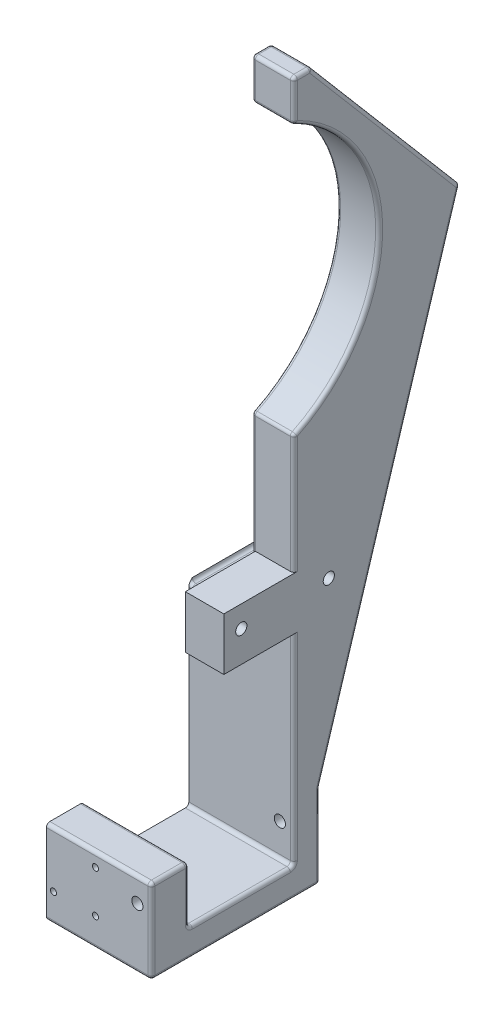
SolidWorks part; units mm, degrees
note: The reader was unsure of these and kept them because the rebuilt part matched: shared geometry of "Sketch12<3>".
ref_plane "Front Plane" through (0, 0, 0) normal (0, 0, 1) x (1, 0, 0)
ref_plane "Top Plane" through (0, 0, 0) normal (0, 1, 0) x (1, 0, 0)
ref_plane "Right Plane" through (0, 0, 0) normal (1, 0, 0) x (0, 0, -1)
sketch "Sketch3" plane through (0, 0, 0) normal (0, 1, 0) x (1, 0, 0)
  line L1 (-55.92, 48.2) -> (0, 48.2)
  line L2 (-55.92, 48.2) -> (-55.92, 0)
  line L3 (-55.92, 0) -> (0, 0)
  line L4 (0, 48.2) -> (0, 0)
  dimension "D1" = 55.92
  dimension "D2" = 48.2
extrude "Boss-Extrude1" add sketch "Sketch3" along normal blind 8
sketch "Sketch4" plane through (0, 8, 0) normal (0, 1, 0) x (1, 0, 0)
  line L0 (-55.92, 0) -> (-55.92, 48.2)
  line L9 (-55.92, 48.2) -> (0, 48.2)
  line L10 (0, 48.2) -> (0, 40.7)
  line L11 (0, 40.7) -> (-48.42, 40.7)
  line L12 (-48.42, 40.7) -> (-48.42, 0)
  line L13 (-48.42, 0) -> (-55.92, 0)
  line L14 (0, 48.2) -> (-55.92, 48.2) construction
  line L15 (-55.92, 48.2) -> (-55.92, 0) construction
  line L16 (-55.92, 0) -> (0, 0) construction
  line L17 (0, 0) -> (0, 48.2) construction
  dimension "D1" = 7.5
extrude "Boss-Extrude2" add sketch "Sketch4" along normal blind 95
sketch "Sketch5" plane through (-48.42, 0, 0) normal (1, 0, 0) x (0, 0, -1)
  line L0 (0, 103) -> (0, 8) construction
  line L1 (0, 82.4) -> (40.7, 82.4)
  line L2 (0, 82.4) -> (0, 17.6)
  line L3 (0, 17.6) -> (40.7, 17.6)
  line L4 (40.7, 82.4) -> (40.7, 17.6)
  line L5 (40.7, 103) -> (40.7, 8) construction
  line L7 (0, 8) -> (40.7, 8) construction
  line L8 (0, 50) -> (40.7, 50) construction
  circle A0 centre (17.2, 12.5) radius 2.75
  circle A1 centre (34.2, 12.5) radius 2.75
  circle A2 centre (34.2, 87.5) radius 2.75
  circle A3 centre (17.2, 87.5) radius 2.75
  dimension "D3" = 5.5
  dimension "D1" = 4.5
  dimension "D2" = 64.8
  dimension "D4" = 17
  dimension "D5" = 5.1
  dimension "D6" = 6.5
  dimension "D7" = 75
extrude "Cut-Extrude1" cut sketch "Sketch5" against normal through all
sketch "Sketch8" plane through (0, 0, 0) normal (1, 0, 0) x (0, 0, -1)
  line L0 (40.7, 103) -> (40.7, 203)
  line L1 (40.7, 203) -> (45.7, 203)
  line L2 (45.7, 203) -> (88.2, 153)
  line L3 (88.2, 153) -> (48.2, 24)
  line L4 (48.2, 24) -> (48.2, 103)
  line L5 (48.2, 103) -> (40.7, 103)
  line L6 (40.7, 103) -> (48.2, 103) construction
  line L7 (48.2, 103) -> (48.2, 0) construction
  line L8 (40.7, 103) -> (40.7, 8) construction
  point P25 (40.7, 153)
  dimension "D1" = 100
  dimension "D2" = 5
  dimension "D3" = 40
  dimension "D4" = 24
extrude "Boss-Extrude4" add sketch "Sketch8" against normal blind 55.92
sketch "Sketch9" plane through (0, 0, 0) normal (1, 0, 0) x (0, 0, -1)
  line L0 (88.2, 153) -> (45.7, 203) construction
  circle A0 centre (22.578, 153) radius 42.5
  dimension "D1" = 85
  dimension "D2" = 50
extrude "Cut-Extrude2" cut sketch "Sketch9" against normal through all
sketch "Sketch10" plane through (0, 0, -40.7) normal (0, 0, 1) x (1, 0, 0)
  line L0 (-55.92, 103) -> (-48.42, 103) construction
  line L1 (-30, 203) -> (-12, 203)
  line L2 (-30, 203) -> (-30, 63)
  line L3 (-30, 63) -> (-12, 63)
  line L4 (-12, 203) -> (-12, 63)
  line L5 (0, 114.5573) -> (0, 191.4427) construction
  line L8 (-55.92, 203) -> (0, 203) construction
  line L10 (-55.92, 203) -> (-42, 203)
  line L11 (-42, 203) -> (-42, 103)
  line L12 (-42, 103) -> (-55.92, 103)
  line L13 (-55.92, 103) -> (-55.92, 203)
  line L14 (-55.92, 191.4427) -> (-55.92, 114.5573) construction
  point P11 (-21, 203)
  dimension "D1" = 18
  dimension "D2" = 42
  dimension "D3" = 21
  dimension "D4" = 140
extrude "Cut-Extrude3" cut sketch "Sketch10" against normal through all
sketch "Sketch11" plane through (0, 8, 0) normal (0, 1, 0) x (1, 0, 0)
  line L0 (0, 0) -> (0, 40.7) construction
  line L1 (0, 0) -> (-48.42, 0)
  line L2 (0, 0) -> (0, 10.7)
  line L3 (0, 10.7) -> (-48.42, 10.7)
  line L4 (-48.42, 0) -> (-48.42, 10.7)
  line L5 (-55.92, 0) -> (-48.42, 0) construction
  line L6 (-48.42, 0) -> (-48.42, 40.7) construction
  dimension "D1" = 10.7
extrude "Boss-Extrude5" add sketch "Sketch11" along normal blind 16
sketch "Sketch12" plane through (0, 0, 0) normal (0, 0, 1) x (1, 0, 0)
  line L0 (-27.96, 20.15) -> (-27.96, -0.9173) construction
  line L1 (-39.96, 20.15) -> (-15.96, 20.15) construction
  line L2 (-48.42, 24) -> (0, 24) construction
  line L3 (-55.92, 0) -> (0, 0) construction
  circle A0 centre (-39.96, 8.15) radius 0.875
  circle A1 centre (-39.96, 20.15) radius 0.875
  circle A2 centre (-27.96, 8.15) radius 0.875
  circle A3 centre (-15.96, 8.15) radius 0.875
  circle A4 centre (-15.96, 20.15) radius 0.875
  point P21 (-27.96, 0)
  dimension "D1" = 1.75
  dimension "D2" = 24
  dimension "D3" = 12
  dimension "D4" = 3.85
extrude "Cut-Extrude7" cut sketch "Sketch12" against normal blind 8
extrude "Cut-Extrude8" cut sketch "Sketch12<3>" along normal blind 5 from surface at -48.2 starting at face at (-27.96, 12, -48.2)
sketch "Sketch12<3>" plane through (0, 0, 0) normal (0, 0, 1) x (1, 0, 0) same geometry as "Sketch12"
fillet "Fillet3" radius 1 80 edges at (-36, 191.4427, -40.7) (-6, 191.4427, -40.7) (-42, 153, -65.078) (-12, 153, -65.078) (-30, 153, -65.078) (-36, 153, -88.2) (-6, 153, -88.2) (-48.96, 103, -72.6961) (-21, 63, -60.293) (-36, 203, -45.7) (-6, 203, -45.7) (-36, 203, -40.7) (-6, 203, -40.7) (-30, 178, -66.95) (-30, 108, -74.2465) (-30, 63, -50.4965) (-12, 178, -66.95) (-12, 108, -74.2465) (-12, 203, -43.2) (-12, 88.7786, -40.7) (-30, 88.7786, -40.7) (-21, 63, -40.7) (-30, 197.2214, -40.7) (-12, 197.2214, -40.7) (-30, 203, -43.2) (-12, 63, -50.4965) (-42, 178, -66.95) (-42, 128, -80.4481) (-42, 203, -43.2) (-42, 197.2214, -40.7) (-45.21, 103, -40.7) (-42, 108.7786, -40.7) (-42, 103, -56.6981) (-48.42, 17.6, -25.7) (-48.42, 8, -25.7) (0, 8, -25.7) (-48.42, 20.8, -10.7) (-24.21, 8, -10.7) (-48.42, 92.7, 0) (0, 16, -10.7) (-48.42, 12.8, -10.7) (-48.42, 20.8, 0) (-24.21, 8, -40.7) (0, 24, -5.35) (-24.21, 24, -10.7) (-48.42, 24, -5.35) (-24.21, 24, 0) (-48.42, 92.7, -40.7) (0, 197.2214, -40.7) (-52.17, 103, 0) (-48.42, 103, -20.35) (-48.42, 12.8, -40.7) (-55.92, 8.8, 0) (-27.96, 0, -48.2) (-52.17, 17.6, 0) (-55.92, 82.4, -20.35) (-52.17, 82.4, 0) (-55.92, 50, -40.7) (-52.17, 82.4, -40.7) (-55.92, 17.6, -20.35) (-52.17, 17.6, -40.7) (-48.42, 17.6, -5.35) (0, 0, -24.1) (-48.42, 82.4, -20.35) (-27.96, 0, 0) (-55.92, 0, -24.1) (-55.92, 103, -36.3481) (-55.92, 12, -48.2) (0, 12, -48.2) (-55.92, 63.5, -60.4481) (-27.96, 24, -48.2) (0, 88.5, -68.2) (0, 178, -66.95) (0, 203, -43.2) (0, 12, 0) (-55.92, 92.7, 0) (0, 61.2786, -40.7) (-6, 114.5573, -40.7) (0, 153, -65.078) (-36, 114.5573, -40.7)
sketch "Sketch14" plane through (0, 0, -48.2) normal (0, 0, -1) x (-1, 0, 0)
  line L0 (1, 23.8485) -> (1, 1) construction
  line L1 (54.92, 23.8485) -> (1, 23.8485) construction
  circle A0 centre (4, 17.2285) radius 1.6
  dimension "D1" = 3.2
  dimension "D2" = 3
  dimension "D3" = 6.62
extrude "Cut-Extrude9" cut sketch "Sketch14" against normal up to surface (48.2 mm away)
sketch "Sketch15" plane through (0, 0, -40.7) normal (0, 0, 1) x (1, 0, 0)
  line L0 (-11, 113.9283) -> (-11, 64) construction
  line L1 (-11, 80.5) -> (0, 80.5)
  line L2 (-11, 80.5) -> (-11, 65.5)
  line L3 (-11, 65.5) -> (0, 65.5)
  line L4 (0, 80.5) -> (0, 65.5)
  line L6 (-1, 8) -> (-47.42, 8) construction
  line L7 (0, 113.9283) -> (0, 9) construction
  dimension "D1" = 57.5
  dimension "D2" = 72.5
extrude "Boss-Extrude6" add sketch "Sketch15" along normal blind 20 and the other way up to next
sketch "Sketch16" plane through (0, 0, 0) normal (1, 0, 0) x (0, 0, -1)
  line L0 (20.7, 65.5) -> (20.7, 80.5) construction
  line L2 (1, 24) -> (9.7, 24) construction
  circle A0 centre (25.69, 74.3259) radius 1.6
  circle A1 centre (50.69, 74.3259) radius 1.6
  dimension "D1" = 3.2
  dimension "D4" = 25
  dimension "D2" = 4.99
  dimension "D3" = 50.3259
extrude "Cut-Extrude10" cut sketch "Sketch16" against normal up to next
sketch "Sketch17" plane through (0, 0, -40.7) normal (0, 0, 1) x (1, 0, 0)
  line L0 (-30, 113.9283) -> (-30, 64) construction
  line L1 (-30, 529.4052) -> (-288.1725, 529.4052)
  line L2 (-30, 529.4052) -> (-30, -248.908)
  line L3 (-30, -248.908) -> (-288.1725, -248.908)
  line L4 (-288.1725, 529.4052) -> (-288.1725, -248.908)
  point P4 (45.9584, 224.1908)
ref_plane "Plane1" through (-30, 0, 0) normal (1, 0, 0) x (0, 0, -1)
sketch "Sketch21" plane through (-30, 0, 0) normal (1, 0, 0) x (0, 0, -1)
  line L0 (45.7, 50) -> (48.2, 54.3301)
  line L1 (48.2, 54.3301) -> (50.7, 50)
  line L2 (50.7, 50) -> (45.7, 50)
  line L3 (43.2, 35) -> (48.2, 35)
  line L4 (48.2, 35) -> (45.7, 30.6699)
  line L5 (45.7, 30.6699) -> (43.2, 35)
  line L6 (45.7, 2.5) -> (40.7, 2.5)
  line L7 (40.7, 2.5) -> (43.2, 6.8301)
  line L8 (43.2, 6.8301) -> (45.7, 2.5)
  line L9 (2.85, 20.5) -> (7.85, 20.5)
  line L10 (7.85, 20.5) -> (5.35, 16.1699)
  line L11 (5.35, 16.1699) -> (2.85, 20.5)
  line L12 (10, 2.5) -> (5, 2.5)
  line L13 (5, 2.5) -> (7.5, 6.8301)
  line L14 (7.5, 6.8301) -> (10, 2.5)
  line L15 (9.7, 24) -> (1, 24) construction
  line L16 (0, 16.6) -> (0, 1) construction
  line L20 (1, 0) -> (47.2, 0) construction
  line L21 (48.2, 1) -> (48.2, 23.8485) construction
  line L22 (40.7, 81.4) -> (40.7, 18.6) construction
  point P17 (4.3053, 6.8301)
  point P28 (0, 0)
  dimension "D1" = 5
  dimension "D2" = 5
  dimension "D3" = 5
  dimension "D4" = 5
  dimension "D5" = 5
  dimension "D6" = 2.5
  dimension "D7" = 3.5
  dimension "D8" = 7.5
  dimension "D9" = 5
  dimension "D10" = 15
  dimension "D11" = 50
  dimension "D12" = 5
  dimension "D13" = 7.5
  dimension "D14" = 5.35
extrude "Cut-Extrude13" cut sketch "Sketch17" against normal through all both and the other way through all
extrude "Cut-Extrude14" cut sketch "Sketch21" along normal blind 15
equation "\"A\"= 55.92mm"
equation "\"D1@Sketch3\"=\"A\""
equation "\"D1@Boss-Extrude4\"=\"A\""
